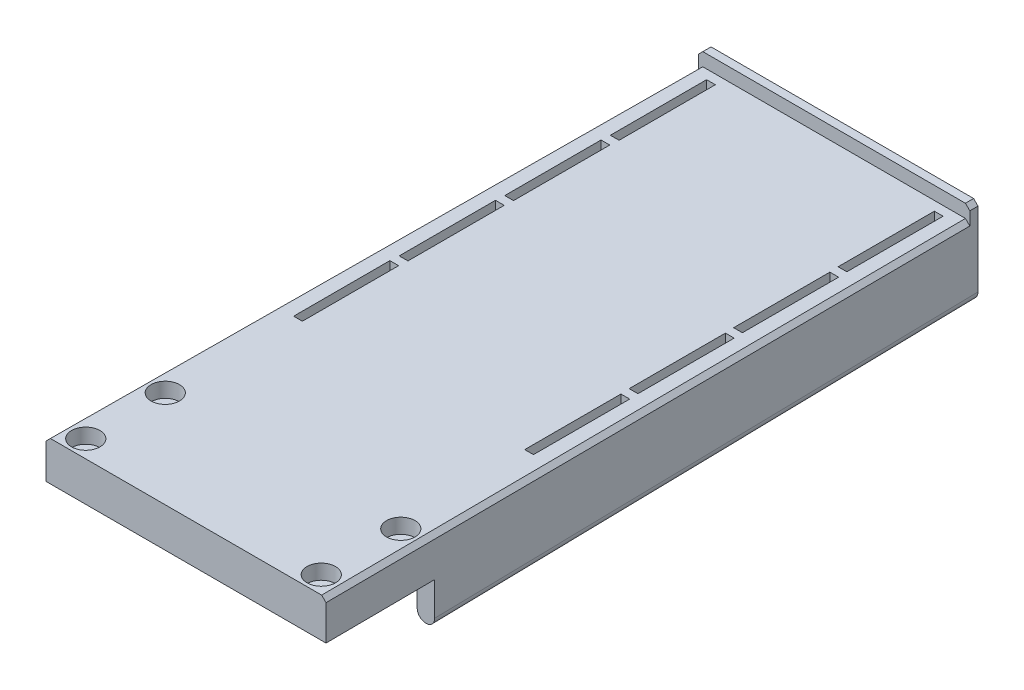
SolidWorks part; units mm, degrees
ref_plane "Front Plane" through (0, 0, 0) normal (0, 0, 1) x (1, 0, 0)
ref_plane "Top Plane" through (0, 0, 0) normal (0, 1, 0) x (1, 0, 0)
ref_plane "Right Plane" through (0, 0, 0) normal (1, 0, 0) x (0, 0, -1)
sketch "Sketch1" plane through (0, 0, 0) normal (0, 1, 0) x (1, 0, 0)
  line L0 (31, 0) -> (-31, 0)
  line L1 (0, 0) -> (0, -150) construction
  line L2 (32, -150) -> (-32, -150)
  line L3 (-32, -150) -> (-31, 0)
  line L4 (32, -150) -> (31, 0)
  dimension "\"neck length" = 150
extrude "Boss-Extrude1" add sketch "Sketch1" along normal blind 19
sketch "Sketch4" plane through (0, 0, 0) normal (1, 0, 0) x (0, 0, -1)
  line L0 (-150, 0) -> (0, 0)
  line L1 (0, 0) -> (0, 2)
  line L2 (0, 19) -> (0, 0) construction
  line L4 (0, 2) -> (-150, 0)
extrude "Cut-Extrude1" cut sketch "Sketch4" against normal through all both and the other way through all
shell "Shell1" thickness 4 removed face at (0, 1, 75)
fillet "Fillet2" 2 edges at (31.5, 1, 75) (27.4999, 1, 75) type full round first side face at (31.5, 10, 75) second side face at (27.4999, 5.5, 75) middle face at (0, 1, 75)
fillet "Fillet3" 2 edges at (-31.5, 1, 75) (-27.4999, 1, 75) type full round first side face at (-31.5, 10, 75) second side face at (-27.4999, 5.5, 75) middle face at (0.0001, 1, 75)
sketch "Sketch5" plane through (0, 19, 0) normal (0, 1, 0) x (1, 0, 0)
  line L0 (-31, 0) -> (-31.0125, -1.8797)
  line L1 (-31, 0) -> (-32, -150) construction
  line L2 (-31.0125, -1.8797) -> (31.0125, -1.8797)
  line L3 (32, -150) -> (31, 0) construction
  line L4 (31.0125, -1.8797) -> (31, 0)
  line L5 (31, 0) -> (-31, 0)
extrude "Boss-Extrude2" add sketch "Sketch5" along normal blind 3
chamfer "Chamfer1" distance 1 angle 45 2 edges at (31.5063, 19, 75.9398) (-31.5063, 19, 75.9398)
chamfer "Chamfer2" distance 1 angle 45 2 edges at (31.0063, 22, 0.9398) (-31.0063, 22, 0.9398)
sketch "Sketch6" plane through (0, 19, 0) normal (0, 1, 0) x (1, 0, 0)
  line L0 (-30.0125, -1.8797) -> (30.0125, -1.8797)
  line L1 (0, -1.8797) -> (0, -197.9912) construction
  line L2 (-31.316, -197.3975) -> (31.316, -197.3975)
  line L3 (31, -150) -> (30.0125, -1.8797) construction
  line L4 (31.316, -197.3975) -> (30.0125, -1.8797)
  line L5 (-30.0125, -1.8797) -> (-31.316, -197.3975)
  line L6 (-30.0125, -1.8797) -> (-31, -150) construction
extrude "Cut-Extrude2" [suppressed] cut sketch "Sketch6" against normal blind 1.6
sketch "Sketch7" plane through (0, 0, 150) normal (0, 0, 1) x (1, 0, 0)
  line L1 (-32, 10) -> (32, 10)
  line L2 (-32, 18) -> (-32, 2) construction
  line L3 (32, 18) -> (32, 2) construction
  line L4 (32, 10) -> (32, 0)
  line L7 (-32, 0) -> (-32, 10)
  line L8 (-32, 0) -> (32, 0)
extrude "Cut-Extrude3" cut sketch "Sketch7" against normal blind 25
sketch "Sketch11" plane through (0, 10, 0) normal (0, -1, 0) x (1, 0, 0)
  line L0 (27.1522, 27.9997) -> (27.1522, 49.9997)
  line L1 (27.0266, 4) -> (25.0266, 4)
  line L2 (27.0266, 4) -> (27.0266, 26)
  line L3 (27.0266, 26) -> (25.0266, 26)
  line L4 (25.0266, 4) -> (25.0266, 26)
  line L5 (27.1522, 27.9997) -> (25.1522, 27.9997)
  line L6 (25.1522, 27.9997) -> (25.1522, 49.9997)
  line L7 (27.1522, 49.9997) -> (25.1522, 49.9997)
  line L8 (27.2779, 51.9993) -> (27.2779, 73.9993)
  line L9 (27.2779, 51.9993) -> (25.2779, 51.9993)
  line L10 (25.2779, 51.9993) -> (25.2779, 73.9993)
  line L11 (27.2779, 73.9993) -> (25.2779, 73.9993)
  line L12 (27.4036, 75.999) -> (27.4036, 97.999)
  line L13 (27.4036, 75.999) -> (25.4036, 75.999)
  line L14 (25.4036, 75.999) -> (25.4036, 97.999)
  line L15 (27.4036, 97.999) -> (25.4036, 97.999)
  line L16 (27.0266, 4) -> (27.1522, 27.9997) construction
  line L17 (0, -11.9167) -> (0, 11.9167) construction
  line L18 (-27.4036, 75.999) -> (-25.4036, 75.999)
  line L19 (-25.4036, 75.999) -> (-25.4036, 97.999)
  line L20 (-27.4036, 97.999) -> (-25.4036, 97.999)
  line L21 (-27.4036, 75.999) -> (-27.4036, 97.999)
  line L22 (-27.2779, 51.9993) -> (-25.2779, 51.9993)
  line L23 (-25.2779, 51.9993) -> (-25.2779, 73.9993)
  line L24 (-27.2779, 73.9993) -> (-25.2779, 73.9993)
  line L25 (-27.2779, 51.9993) -> (-27.2779, 73.9993)
  line L26 (-27.1522, 27.9997) -> (-25.1522, 27.9997)
  line L27 (-25.1522, 27.9997) -> (-25.1522, 49.9997)
  line L28 (-27.1522, 49.9997) -> (-25.1522, 49.9997)
  line L29 (-27.1522, 27.9997) -> (-27.1522, 49.9997)
  line L30 (-27.0266, 26) -> (-25.0266, 26)
  line L31 (-25.0266, 4) -> (-25.0266, 26)
  line L32 (-27.0266, 4) -> (-25.0266, 4)
  line L33 (-27.0266, 4) -> (-27.0266, 26)
  line L34 (27.1522, -95.0215) -> (27.1522, -73.0215)
  line L35 (-25.0266, -119.0211) -> (-25.0266, -97.0211)
  line L36 (-27.1522, -73.0215) -> (-25.1522, -73.0215)
  line L37 (27.0266, -119.0211) -> (25.0266, -119.0211)
  line L38 (27.0266, -97.0211) -> (25.0266, -97.0211)
  line L39 (27.4036, -47.0221) -> (25.4036, -47.0221)
  line L40 (-27.4036, -47.0221) -> (-25.4036, -47.0221)
  line L41 (27.4036, -25.0221) -> (25.4036, -25.0221)
  line L42 (27.1522, -73.0215) -> (25.1522, -73.0215)
  line L43 (-27.4036, -25.0221) -> (-25.4036, -25.0221)
  line L44 (-27.0266, -119.0211) -> (-27.0266, -97.0211)
  line L45 (27.0266, -119.0211) -> (27.0266, -97.0211)
  line L46 (25.0266, -119.0211) -> (25.0266, -97.0211)
  line L47 (27.2779, -49.0218) -> (25.2779, -49.0218)
  line L48 (27.2779, -71.0218) -> (25.2779, -71.0218)
  line L49 (-25.4036, -47.0221) -> (-25.4036, -25.0221)
  line L50 (25.1522, -95.0215) -> (25.1522, -73.0215)
  line L51 (-27.4036, -47.0221) -> (-27.4036, -25.0221)
  line L52 (-25.2779, -71.0218) -> (-25.2779, -49.0218)
  line L53 (-25.1522, -95.0215) -> (-25.1522, -73.0215)
  line L54 (-27.0266, -97.0211) -> (-25.0266, -97.0211)
  line L55 (-27.0266, -119.0211) -> (-25.0266, -119.0211)
  line L56 (-27.2779, -49.0218) -> (-25.2779, -49.0218)
  line L57 (27.1522, -95.0215) -> (25.1522, -95.0215)
  line L58 (27.4036, -47.0221) -> (27.4036, -25.0221)
  line L59 (27.2779, -71.0218) -> (27.2779, -49.0218)
  line L60 (-27.2779, -71.0218) -> (-25.2779, -71.0218)
  line L61 (-27.2779, -71.0218) -> (-27.2779, -49.0218)
  line L62 (25.2779, -71.0218) -> (25.2779, -49.0218)
  line L63 (25.4036, -47.0221) -> (25.4036, -25.0221)
  line L64 (-27.1522, -95.0215) -> (-25.1522, -95.0215)
  line L65 (-27.1522, -95.0215) -> (-27.1522, -73.0215)
  dimension "D1" = 22
  dimension "D2" = 2
  dimension "D4" = 24
  dimension "D3" = 4
extrude "Cut-Extrude4" cut sketch "Sketch11" against normal through all
hole_wizard "CBORE for M3 Hex Socket Head Cap Screw1" positions "Sketch12" profile "Sketch13" counterbore size "M3" standard "ISO" end condition through all
sketch "Sketch12" plane through (75.2969, 19, 61.2992) normal (0, 1, 0) x (1, 0, 0)
  point P0 (-102.2096, -66.5318)
  point P1 (-102.2096, -84.7008)
  point P2 (-48.3841, -84.7008)
  point P3 (-48.3841, -66.5318)
sketch "Sketch13" plane through (-26.9127, 19, 127.831) normal (1, 0, 0) x (0, 0, 1)
  line L0 (0, 0) -> (0, 18.6667)
  line L1 (0, 18.6667) -> (1.45, 18.6667)
  line L2 (1.45, 18.6667) -> (1.45, 3.4)
  line L3 (1.45, 3.4) -> (3.25, 3.4)
  line L4 (3.25, 3.4) -> (3.25, 0)
  line L5 (3.25, 0) -> (0, 0)
  line L6 (0, -6.35) -> (0, 107.95) construction
  dimension "Thru Hole Dia." = 2.9
  dimension "Thru Hole Depth" = 18.6667
  dimension "C'Bore Dia." = 6.5
  dimension "C'Bore Depth" = 3.4
equation "\"neck length\"= 200mm"
